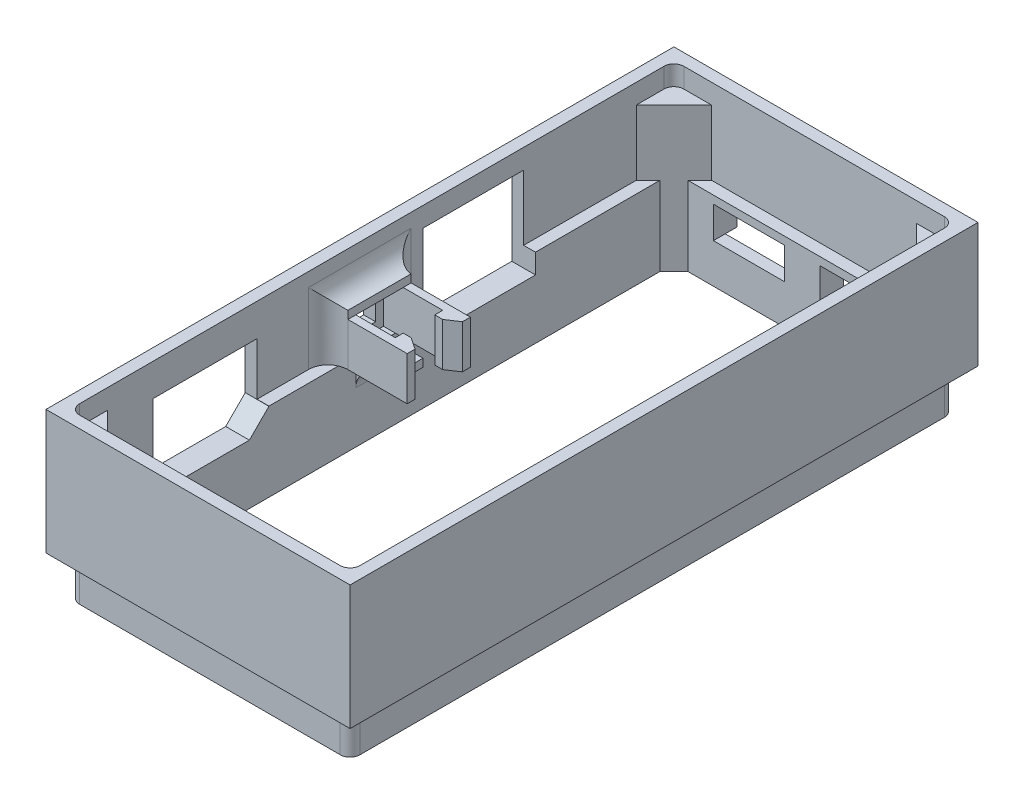
SolidWorks part; units mm, degrees
ref_plane "Front Plane" through (0, 0, 0) normal (0, 0, 1) x (1, 0, 0)
ref_plane "Top Plane" through (0, 0, 0) normal (0, 1, 0) x (1, 0, 0)
ref_plane "Right Plane" through (0, 0, 0) normal (1, 0, 0) x (0, 0, -1)
sketch "Sketch1" plane through (0, 0, 0) normal (0, 1, 0) x (1, 0, 0)
  line L1 (0, 0) -> (-71, 0)
  line L2 (0, 0) -> (0, 153)
  line L3 (0, 153) -> (-71, 153)
  line L4 (-71, 0) -> (-71, 153)
  line L5 (-68, 150) -> (-3, 150)
  line L6 (-68, 150) -> (-68, 3)
  line L7 (-68, 3) -> (-3, 3)
  line L8 (-3, 150) -> (-3, 3)
  point P9 (-35.5, 0)
  dimension "D1" = 71
  dimension "D2" = 153
  dimension "D3" = 3
  dimension "D4" = 3
  dimension "D5" = 3
  dimension "D6" = 3
extrude "Boss-Extrude1" add sketch "Sketch1" along normal blind 10
sketch "Sketch2" plane through (0, 10, 0) normal (0, 1, 0) x (1, 0, 0)
  line L0 (-71, 153) -> (-71, 0) construction
  line L1 (-74, 156) -> (3, 156)
  line L2 (-74, 156) -> (-74, -3)
  line L3 (-74, -3) -> (3, -3)
  line L4 (3, 156) -> (3, -3)
  line L7 (-71, 153) -> (0, 153)
  line L8 (-71, 153) -> (-71, 0)
  line L9 (-71, 0) -> (0, 0)
  line L10 (0, 153) -> (0, 0)
  dimension "D1" = 159
  dimension "D2" = 77
  dimension "D3" = 3
  dimension "D4" = 3
extrude "Boss-Extrude2" add sketch "Sketch2" along normal blind 60 separate body
sketch "Sketch3" plane through (0, 10, 0) normal (0, 1, 0) x (1, 0, 0)
  line L4 (-68, 150) -> (-68, 3) construction
  line L5 (-68, 3) -> (-3, 3) construction
  line L6 (-3, 3) -> (-3, 150) construction
  line L7 (-3, 150) -> (-68, 150) construction
  line L8 (0, 0) -> (0, 153)
  line L9 (0, 153) -> (-71, 153)
  line L10 (-71, 153) -> (-71, 0)
  line L11 (-71, 0) -> (0, 0)
  line L12 (0, 0) -> (0, 153)
  line L13 (0, 153) -> (-71, 153)
  line L14 (-71, 153) -> (-71, 0)
  line L15 (-71, 0) -> (0, 0)
  line L16 (-68, 150) -> (-68, 3)
  line L17 (-68, 3) -> (-3, 3)
  line L18 (-3, 3) -> (-3, 150)
  line L19 (-3, 150) -> (-68, 150)
  dimension "D1" = 0
extrude "Boss-Extrude3" add sketch "Sketch3" along normal blind 10
sketch "Sketch7" plane through (0, 0, 0) normal (0, -1, 0) x (1, 0, 0)
  line L0 (-68, -6.5355) -> (-64.4645, -3)
  line L1 (-68, -150) -> (-68, -3) construction
  line L2 (-68, -3) -> (-3, -3) construction
  dimension "D1" = 45
  dimension "D2" = 5
rib "Rib17" sketch "Sketch7" sketch "Sketch7" thickness 60 extrusion direction parallel to sketch draft on no parameters "D1"=60
sketch "Sketch9" plane through (0, 0, 0) normal (0, -1, 0) x (1, 0, 0)
  line L0 (-68, -146.4645) -> (-64.4645, -150)
  line L1 (-68, -150) -> (-68, -6.5355) construction
  line L2 (-3, -150) -> (-68, -150) construction
  dimension "D1" = 45
  dimension "D2" = 5
rib "Rib22" sketch "Sketch9" sketch "Sketch9" thickness 60 extrusion direction parallel to sketch draft on no parameters "D1"=60
sketch "Sketch10" plane through (0, 0, 0) normal (0, -1, 0) x (1, 0, 0)
  line L0 (-6.5355, -150) -> (-3, -146.4645)
  line L1 (-3, -150) -> (-64.4645, -150) construction
  line L2 (-3, -3) -> (-3, -150) construction
  dimension "D1" = 45
  dimension "D2" = 5
rib "Rib23" sketch "Sketch10" sketch "Sketch10" thickness 60 extrusion direction parallel to sketch draft on no parameters "D1"=60
sketch "Sketch11" plane through (0, 0, 0) normal (0, -1, 0) x (1, 0, 0)
  line L0 (-6.5355, -3) -> (-3, -6.5355)
  line L1 (-64.4645, -3) -> (-3, -3) construction
  line L2 (-3, -3) -> (-3, -146.4645) construction
  dimension "D1" = 5
  dimension "D2" = 45
rib "Rib24" sketch "Sketch11" sketch "Sketch11" thickness 60 extrusion direction parallel to sketch draft on no parameters "D1"=60
fillet "Fillet1" radius 2.5 4 edges at (-71, 5, 0) (0, 5, 0) (0, 5, -153) (-71, 5, -153)
fillet "Fillet2" radius 3 4 edges at (0, 65, -153) (-71, 65, -153) (0, 65, 0) (-71, 65, 0)
sketch "Sketch12" plane through (0, 0, -156) normal (0, 0, -1) x (-1, 0, 0)
  line L0 (35.5, 10) -> (35.5, 70) construction
  line L1 (2.5, 10) -> (68.5, 10) construction
  line L2 (-3, 70) -> (74, 70) construction
  line L3 (31, 10) -> (40, 10) construction
  line L4 (-3, 10) -> (74, 10) construction
  line L6 (31, 10) -> (13, 10)
  line L7 (31, 10) -> (31, 18)
  line L8 (31, 18) -> (13, 18)
  line L9 (13, 10) -> (13, 18)
  line L10 (40, 10) -> (58, 10)
  line L11 (40, 10) -> (40, 18)
  line L12 (40, 18) -> (58, 18)
  line L13 (58, 10) -> (58, 18)
  point P10 (35.5, 10)
  dimension "D1" = 9
  dimension "D2" = 18
  dimension "D3" = 8
extrude "Cut-Extrude1" cut sketch "Sketch12" against normal blind 10
sketch "Sketch13" plane through (-74, 0, 0) normal (-1, 0, 0) x (0, 0, 1)
  line L13 (-47.45, 19.9497) -> (-42.5003, 15)
  line L14 (-79.45, 31) -> (-67.45, 31)
  line L15 (-79.45, 31) -> (-79.45, 20)
  line L16 (-79.45, 20) -> (-67.45, 20)
  line L17 (-67.45, 31) -> (-67.45, 20)
  line L18 (-47.45, 33.3) -> (-21.05, 33.3)
  line L19 (-47.45, 33.3) -> (-47.45, 19.9497)
  line L20 (-42.5003, 15) -> (-25.9997, 15)
  line L21 (-21.05, 33.3) -> (-21.05, 19.9497)
  line L22 (-21.05, 19.9497) -> (-25.9997, 15)
  line L23 (3, 70) -> (3, 10) construction
  line L24 (-114.95, 36.5) -> (-89.45, 36.5)
  line L25 (-114.95, 36.5) -> (-114.95, 15)
  line L26 (-114.95, 15) -> (-89.45, 15)
  line L27 (-89.45, 36.5) -> (-89.45, 15)
  line L29 (-156, 10) -> (3, 10) construction
  dimension "D1" = 12
  dimension "D2" = 11
  dimension "D3" = 24.05
  dimension "D4" = 5
  dimension "D5" = 135
  dimension "D6" = 13.3503
  dimension "D7" = 26.4
  dimension "D8" = 18.3
  dimension "D9" = 20
  dimension "D10" = 10
  dimension "D11" = 10
  dimension "D12" = 25.5
  dimension "D13" = 21.5
  dimension "D14" = 5
extrude "Cut-Extrude2" cut sketch "Sketch13" against normal blind 10
sketch "Sketch14" plane through (0, 70, 0) normal (0, 1, 0) x (1, 0, 0)
  line L4 (-74, 156) -> (-74, -3)
  line L5 (-74, -3) -> (3, -3)
  line L6 (3, -3) -> (3, 156)
  line L7 (3, 156) -> (-74, 156)
  line L8 (-74, 156) -> (-74, -3)
  line L9 (-74, -3) -> (3, -3)
  line L10 (3, -3) -> (3, 156)
  line L11 (3, 156) -> (-74, 156)
  dimension "D1" = 0
extrude "Cut-Extrude3" cut sketch "Sketch14" against normal blind 28.5
sketch "Sketch15" plane through (0, 41.5, 0) normal (0, 1, 0) x (1, 0, 0)
  line L0 (3, 156) -> (-74, 156) construction
  line L1 (-71, 0) -> (0, 0)
  line L2 (-71, 0) -> (-71, 153)
  line L3 (-71, 153) -> (0, 153)
  line L4 (0, 0) -> (0, 153)
  line L5 (3, -3) -> (3, 156) construction
  line L6 (-74, 156) -> (-74, -3) construction
  line L7 (-74, -3) -> (3, -3) construction
  dimension "D1" = 3
  dimension "D2" = 3
  dimension "D3" = 3
  dimension "D4" = 3
extrude "Cut-Extrude4" cut sketch "Sketch15" against normal blind 5
fillet "Fillet3" radius 2.5 4 edges at (0, 39, 0) (-71, 39, 0) (0, 39, -153) (-71, 39, -153)
sketch "Sketch16" plane through (-71, 0, 0) normal (1, 0, 0) x (0, 0, -1)
  line L0 (67.45, 31) -> (67.45, 20) construction
  line L1 (67.45, 31) -> (65.45, 31)
  line L2 (67.45, 31) -> (67.45, 20)
  line L3 (67.45, 20) -> (65.45, 20)
  line L4 (65.45, 31) -> (65.45, 20)
  line L5 (89.45, 20) -> (47.45, 20) construction
  line L6 (79.45, 20) -> (79.45, 31) construction
  line L7 (79.45, 31) -> (81.45, 31)
  line L8 (79.45, 31) -> (79.45, 20)
  line L9 (79.45, 20) -> (81.45, 20)
  line L10 (81.45, 31) -> (81.45, 20)
  dimension "D1" = 2
  dimension "D2" = 2
  dimension "D3" = 11
extrude "Boss-Extrude4" add sketch "Sketch16" along normal blind 17
sketch "Sketch17" plane through (0, 31, 0) normal (0, 1, 0) x (1, 0, 0)
  line L0 (-54, 79.45) -> (-56, 79.45)
  line L1 (-54, 79.45) -> (-71, 79.45) construction
  line L2 (-56, 79.45) -> (-56, 77.45)
  line L5 (-56, 67.45) -> (-56, 69.45)
  line L6 (-51, 65.45) -> (-51, 67.45)
  line L8 (-54, 65.45) -> (-54, 67.45)
  line L9 (-54, 65.45) -> (-51, 65.45)
  line L11 (-56, 77.45) -> (-54, 77.45)
  line L12 (-54, 77.45) -> (-51, 79.45)
  line L13 (-54, 81.45) -> (-71, 81.45) construction
  line L14 (-54, 81.45) -> (-51, 81.45)
  line L15 (-54, 81.45) -> (-54, 79.45)
  line L17 (-51, 81.45) -> (-51, 79.45)
  line L18 (-54, 81.45) -> (-54, 79.45) construction
  line L19 (-71, 79.45) -> (-71, 67.45) construction
  line L20 (-71, 150.5) -> (-71, 2.5) construction
  line L21 (-71, 73.45) -> (-54, 73.45) construction
  line L22 (-54, 73.45) -> (-54, 67.45) construction
  line L23 (-54, 67.45) -> (-54, 65.45) construction
  line L24 (-54, 67.45) -> (-71, 67.45) construction
  line L25 (-54, 69.45) -> (-51, 67.45)
  line L26 (-56, 69.45) -> (-54, 69.45)
  line L27 (-54, 67.45) -> (-56, 67.45)
  point P12 (0, 0)
  dimension "D1" = 2
  dimension "D2" = 2
  dimension "D4" = 5
  dimension "D5" = 2
extrude "Boss-Extrude5" add sketch "Sketch17" against normal blind 11
sketch "Sketch19" plane through (-68, 0, 0) normal (1, 0, 0) x (0, 0, -1)
  line L0 (67.45, 20) -> (67.45, 31) construction
  line L1 (69.45, 20) -> (77.45, 20)
  line L3 (69.45, 18) -> (77.45, 18)
  line L7 (77.45, 20) -> (77.45, 18)
  line L8 (69.45, 20) -> (69.45, 18)
  line L9 (79.45, 20) -> (67.45, 20) construction
  dimension "D1" = 2
  dimension "D2" = 8
  dimension "D3" = 2
extrude "Boss-Extrude7" add sketch "Sketch19" along normal blind 9
sketch "Sketch20" plane through (-74, 0, 0) normal (-1, 0, 0) x (0, 0, 1)
  line L0 (-79.45, 31) -> (-79.45, 20) construction
  line L1 (-79.45, 31) -> (-77.45, 31)
  line L2 (-79.45, 31) -> (-79.45, 20)
  line L3 (-79.45, 20) -> (-77.45, 20)
  line L4 (-77.45, 29) -> (-77.45, 22)
  line L5 (-79.45, 20) -> (-67.45, 20) construction
  line L6 (-67.45, 31) -> (-79.45, 31) construction
  line L7 (-67.45, 31) -> (-69.45, 31)
  line L8 (-67.45, 31) -> (-67.45, 20)
  line L9 (-67.45, 20) -> (-69.45, 20)
  line L10 (-69.45, 29) -> (-69.45, 22)
  line L11 (-67.45, 20) -> (-67.45, 31) construction
  line L13 (-77.45, 31) -> (-69.45, 31)
  line L15 (-77.45, 29) -> (-69.45, 29)
  line L17 (-77.45, 20) -> (-69.45, 20)
  line L19 (-77.45, 22) -> (-69.45, 22)
  dimension "D1" = 2
  dimension "D2" = 2
  dimension "D3" = 7
  dimension "D4" = 2
  dimension "D5" = 2
  dimension "D6" = 8
extrude "Boss-Extrude8" add sketch "Sketch20" against normal blind 3
sketch "Sketch21" plane through (-71, 0, 0) normal (1, 0, 0) x (0, 0, -1)
  line L1 (65.45, 31) -> (81.45, 31)
  line L2 (65.45, 31) -> (65.45, 33)
  line L3 (65.45, 33) -> (81.45, 33)
  line L4 (81.45, 31) -> (81.45, 33)
  line L7 (81.45, 20) -> (81.45, 31) construction
  line L8 (81.45, 31) -> (79.45, 31) construction
  dimension "D1" = 2
  dimension "D2" = 16
extrude "Boss-Extrude9" add sketch "Sketch21" along normal blind 5
fillet "Fillet4" radius 5 4 edges at (-68, 18, -73.45) (-71, 33, -73.45) (-71, 26.5, -81.45) (-71, 26.5, -65.45)
